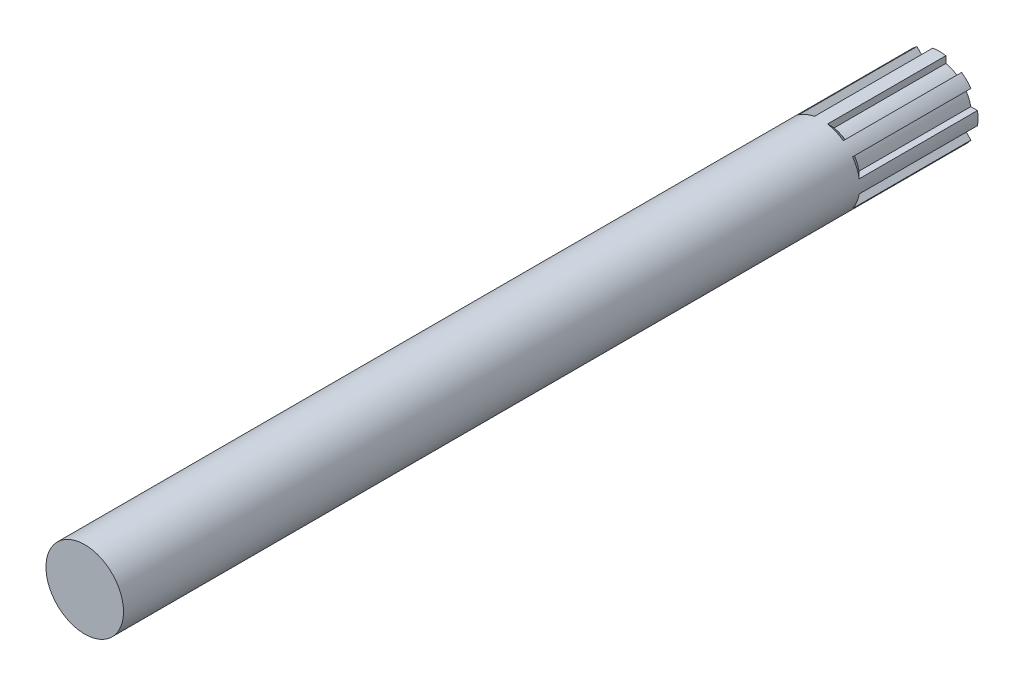
SolidWorks part; units mm, degrees
material "Cast Stainless Steel"
ref_plane "Front Plane" through (0, 0, 0) normal (0, 0, 1) x (1, 0, 0)
ref_plane "Top Plane" through (0, 0, 0) normal (0, 1, 0) x (1, 0, 0)
ref_plane "Right Plane" through (0, 0, 0) normal (1, 0, 0) x (0, 0, -1)
sketch "Sketch1" plane through (0, 0, 0) normal (0, 0, 1) x (1, 0, 0)
  circle A0 centre (0, 0) radius 2.95
  dimension "D1" = 5.9
extrude "Boss-Extrude1" add sketch "Sketch1" along normal blind 65
sketch "Sketch2" plane through (0, 0, 0) normal (0, 0, -1) x (-1, 0, 0)
  line L0 (0, 2.95) -> (0, -2.95) construction
  line L1 (-0.5, 2.3984) -> (-0.5, 2.9073)
  line L2 (0.5, 2.3984) -> (0.5, 2.9073)
  line L3 (1.3424, 2.0495) -> (1.7022, 2.4093)
  line L4 (2.0495, 1.3424) -> (2.4093, 1.7022)
  line L5 (2.3984, 0.5) -> (2.9073, 0.5)
  line L6 (2.3984, -0.5) -> (2.9073, -0.5)
  line L7 (2.0495, -1.3424) -> (2.4093, -1.7022)
  line L8 (1.3424, -2.0495) -> (1.7022, -2.4093)
  line L9 (0.5, -2.3984) -> (0.5, -2.9073)
  line L10 (-0.5, -2.3984) -> (-0.5, -2.9073)
  line L11 (-1.3424, -2.0495) -> (-1.7022, -2.4093)
  line L12 (-2.0495, -1.3424) -> (-2.4093, -1.7022)
  line L13 (-2.3984, -0.5) -> (-2.9073, -0.5)
  line L14 (-2.3984, 0.5) -> (-2.9073, 0.5)
  line L15 (-2.0495, 1.3424) -> (-2.4093, 1.7022)
  line L16 (-1.3424, 2.0495) -> (-1.7022, 2.4093)
  circle A0 centre (0, 0) radius 2.45
  circle A1 centre (0, 0) radius 2.95
  circle A2 centre (0, 0) radius 2.95
  circle A3 centre (0, 0) radius 2.45
  circle A4 centre (0, 0) radius 2.95
  circle A5 centre (0, 0) radius 2.45
  circle A6 centre (0, 0) radius 2.95
  circle A7 centre (0, 0) radius 2.45
  circle A8 centre (0, 0) radius 2.95
  circle A9 centre (0, 0) radius 2.45
  circle A10 centre (0, 0) radius 2.95
  circle A11 centre (0, 0) radius 2.45
  circle A12 centre (0, 0) radius 2.95
  circle A13 centre (0, 0) radius 2.45
  circle A14 centre (0, 0) radius 2.95
  circle A15 centre (0, 0) radius 2.45
  circle A16 centre (0, 0) radius 2.95
  point P54 (0, 0)
  circle M5 centre (0, 0) radius 2.95
  dimension "D2" = 0.5
  dimension "D3" = 1
  dimension "D1" = 0
  dimension "D4" = 8
extrude "Cut-Extrude1" cut sketch "Sketch2" against normal blind 8 contours A0 L15 L14 M5 | A0 L1 L16 M5 | A0 L3 L2 M5 | A0 L5 L4 M5 | A0 L7 L6 M5 | A0 L9 L8 M5 | A0 L11 L10 M5 | A0 L13 L12 M5 region at (1.0314, 2.4901, 0) region at (-1.0314, 2.4901, 0) region at (2.4901, 1.0314, 0) region at (-2.4901, 1.0314, 0) region at (2.4901, -1.0314, 0) region at (-2.4901, -1.0314, 0) region at (1.0314, -2.4901, 0) region at (-1.0314, -2.4901, 0)
chamfer "Chamfer1" distance 1 angle 45 8 edges at (-1.1289, -2.7254, 8) (-2.7254, -1.1289, 8) (-2.7254, 1.1289, 8) (-1.1289, 2.7254, 8) (1.1289, -2.7254, 8) (2.7254, -1.1289, 8) (2.7254, 1.1289, 8) (1.1289, 2.7254, 8)
sketch3d "3DSketch1"
  line L0 (0, 0, 0) -> (0, 0, 65)
  line L1 (0, 0, 65) -> (0, 0, 9) construction
